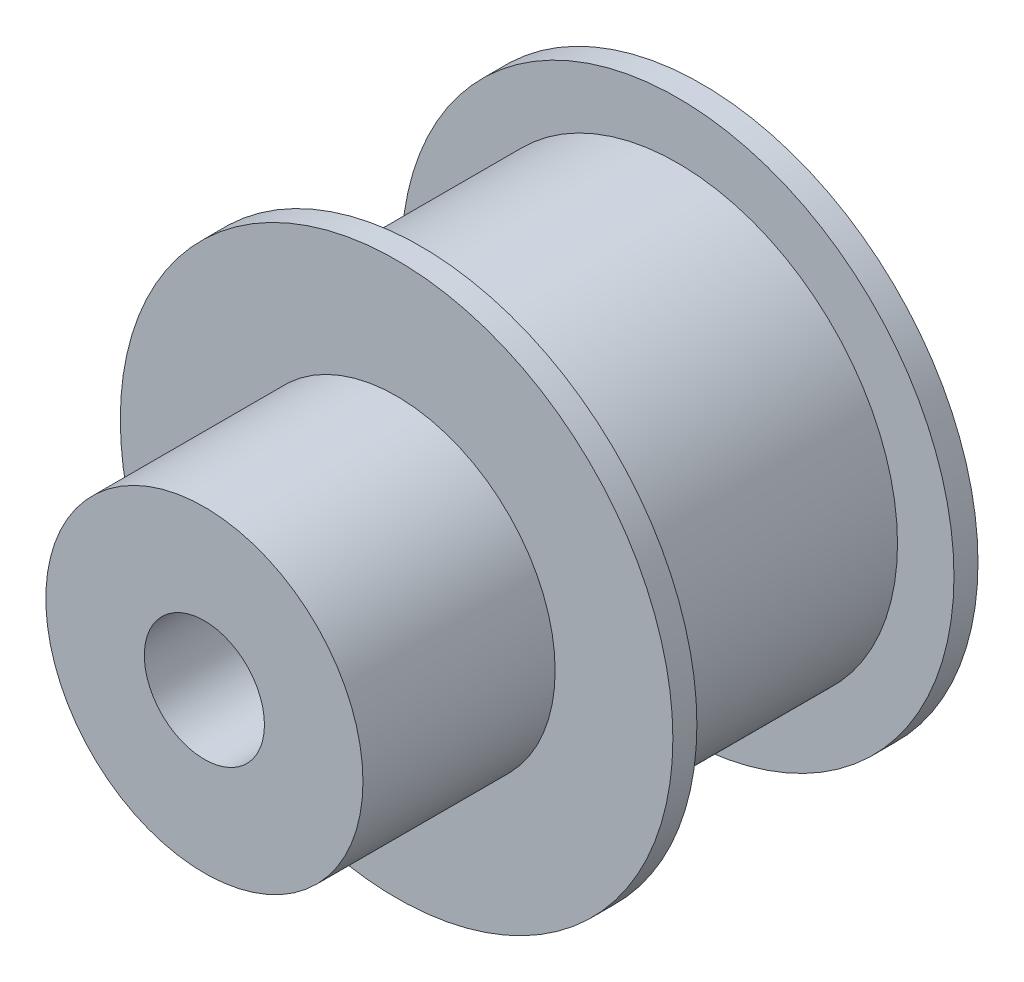
SolidWorks part; units mm, degrees
ref_plane "Спереди" through (0, 0, 0) normal (0, 0, 1) x (1, 0, 0)
ref_plane "Сверху" through (0, 0, 0) normal (0, 1, 0) x (1, 0, 0)
ref_plane "Справа" through (0, 0, 0) normal (1, 0, 0) x (0, 0, -1)
sketch "Эскиз1" plane through (0, 0, 0) normal (0, 0, 1) x (1, 0, 0)
  circle A0 centre (0, 0) radius 11.5
  dimension "D1" = 23
extrude "Бобышка-Вытянуть1" add sketch "Эскиз1" along normal blind 1
sketch "Эскиз2" plane through (0, 0, 1) normal (0, 0, 1) x (1, 0, 0)
  circle A0 centre (0, 0) radius 9.15
  dimension "D1" = 18.3
extrude "Бобышка-Вытянуть2" add sketch "Эскиз2" along normal blind 10.7
sketch "Эскиз3" plane through (0, 0, 11.7) normal (0, 0, 1) x (1, 0, 0)
  circle A0 centre (0, 0) radius 11.5
  dimension "D1" = 23
extrude "Бобышка-Вытянуть3" add sketch "Эскиз3" along normal blind 1
sketch "Эскиз4" plane through (0, 0, 12.7) normal (0, 0, 1) x (1, 0, 0)
  circle A0 centre (0, 0) radius 6.6
  dimension "D1" = 13.2
extrude "Бобышка-Вытянуть4" add sketch "Эскиз4" along normal blind 8
sketch "Эскиз5" plane through (0, 0, 20.7) normal (0, 0, 1) x (1, 0, 0)
  circle A0 centre (0, 0) radius 2.5
  dimension "D1" = 5
extrude "Вырез-Вытянуть1" cut sketch "Эскиз5" against normal through all
